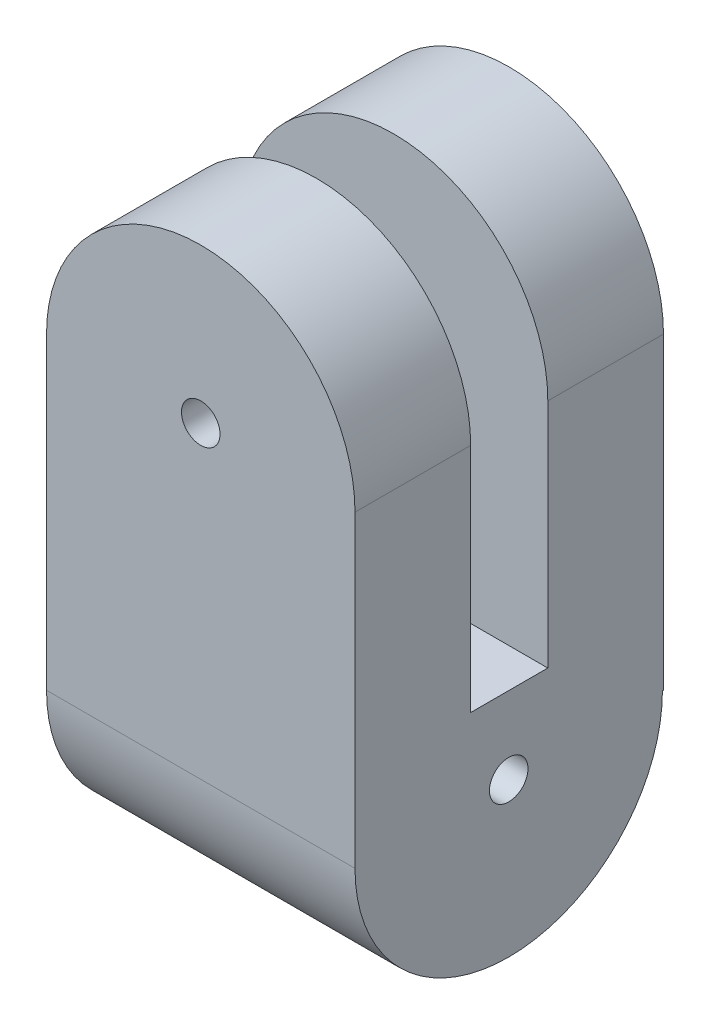
SolidWorks part; units mm, degrees
ref_plane "Front Plane" through (0, 0, 0) normal (0, 0, 1) x (1, 0, 0)
ref_plane "Top Plane" through (0, 0, 0) normal (0, 1, 0) x (1, 0, 0)
ref_plane "Right Plane" through (0, 0, 0) normal (1, 0, 0) x (0, 0, -1)
sketch "Sketch1" plane through (0, 0, 0) normal (0, 0, 1) x (1, 0, 0)
  line L0 (-10, -15) -> (10, -15)
  line L1 (-10, -15) -> (-10, 5)
  line L2 (10, -15) -> (10, 5)
  arc A0 (10, 5) -> (-10, 5) centre (0, 5) ccw
  dimension "D2" = 10
  dimension "D1" = 20
  dimension "D3" = 10
  dimension "D4" = 5
extrude "Boss-Extrude1" add sketch "Sketch1" along normal mid plane 20
sketch "Sketch2" plane through (0, 0, 0) normal (1, 0, 0) x (0, 0, -1)
  line L0 (-2.5, 15) -> (2.5, 15)
  line L1 (-2.5, 15) -> (-2.5, -10)
  line L2 (-2.5, -10) -> (2.5, -10)
  line L3 (2.5, 15) -> (2.5, -10)
  line L4 (10, 15) -> (-10, 15) construction
  dimension "D1" = 25
  dimension "D2" = 5
  dimension "D3" = 0
extrude "Cut-Extrude1" cut sketch "Sketch2" against normal mid plane 20
sketch "Sketch3" plane through (0, 0, 10) normal (0, 0, 1) x (1, 0, 0)
  circle A0 centre (0, 5) radius 1.25
  arc A2 (10, 5) -> (-10, 5) centre (0, 5) ccw construction
  dimension "D1" = 2.5
extrude "Cut-Extrude2" cut sketch "Sketch3" against normal through all
sketch "Sketch6" plane through (10, 0, 0) normal (1, 0, 0) x (0, 0, -1)
  line L0 (-10, -15) -> (9.9325, -15)
  line L1 (-10, -15) -> (10, -15) construction
  line L2 (-10, -15) -> (-10, 5) construction
  arc A0 (-10, -15) -> (9.9325, -15) centre (-0.0337, -15) ccw
  dimension "D1" = 0
  dimension "D2" = 0
extrude "Boss-Extrude3" add sketch "Sketch6" against normal blind 20
sketch "Sketch7" plane through (10, 0, 0) normal (1, 0, 0) x (0, 0, -1)
  circle A0 centre (-0.0337, -15) radius 1.25
  arc A1 (-10, -15) -> (9.9325, -15) centre (-0.0337, -15) ccw construction
  dimension "D1" = 2.5
extrude "Cut-Extrude3" cut sketch "Sketch7" against normal blind 20
ref_axis "Axis1" through (0, 5, -10.1003) along (0, 0, 1)
ref_axis "Axis2" through (-10, -15, 0.0337) along (1, 0, 0)
ref_point "Point1"
ref_point "Point2"
